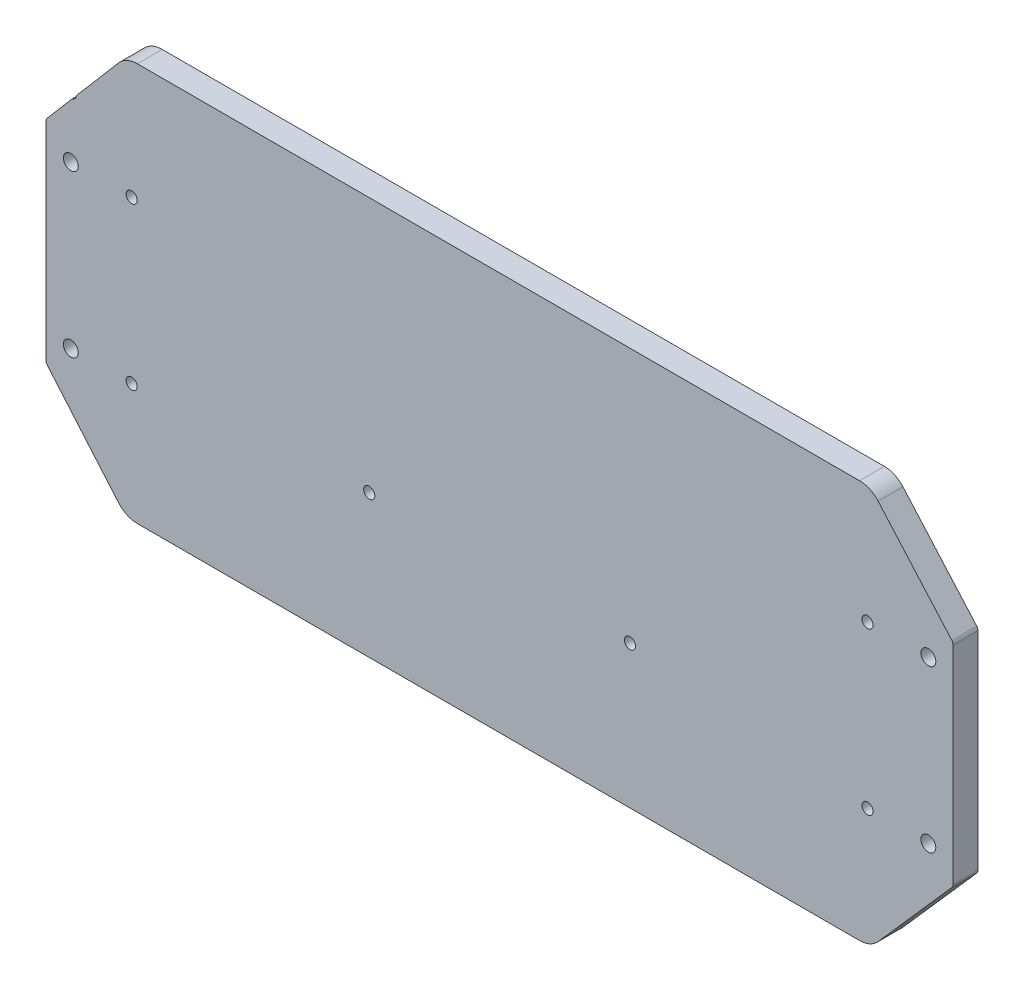
SolidWorks part; units mm, degrees
ref_plane "Plan de face" through (0, 0, 0) normal (0, 0, 1) x (1, 0, 0)
ref_plane "Plan de dessus" through (0, 0, 0) normal (0, 1, 0) x (1, 0, 0)
ref_plane "Plan de droite" through (0, 0, 0) normal (1, 0, 0) x (0, 0, -1)
sketch "Esquisse1" plane through (0, 0, 0) normal (0, 0, 1) x (1, 0, 0)
  line L0 (-182.2, 42.5) -> (-150, 80.2)
  line L1 (-182.2, 42.5) -> (183.2, 42.5)
  line L2 (-182.2, 42.5) -> (-182.2, -42.5)
  line L3 (-182.2, -42.5) -> (183.2, -42.5)
  line L4 (183.2, 42.5) -> (183.2, -42.5)
  line L5 (-150, 80.2) -> (150, 80.2)
  line L6 (-150, 80.2) -> (-150, 42.5)
  line L7 (-150, 42.5) -> (150, 42.5)
  line L8 (150, 80.2) -> (150, 42.5)
  line L9 (-150, -42.5) -> (150, -42.5)
  line L10 (-150, -42.5) -> (-150, -80.2)
  line L11 (-150, -80.2) -> (150, -80.2)
  line L12 (150, -42.5) -> (150, -80.2)
  line L13 (150, 80.2) -> (183.2, 42.5)
  line L14 (183.2, -42.5) -> (150, -80.2)
  line L15 (-150, -80.2) -> (-182.2, -42.5)
  dimension "D1" = 85
  dimension "D2" = 365.4
  dimension "D3" = 300
  dimension "D4" = 300
  dimension "D5" = 32.2
  dimension "D6" = 32.2
  dimension "D7" = 37.7
  dimension "D8" = 37.7
  dimension "D9" = 150
  dimension "D10" = 42.5
extrude "Boss.-Extru.1" add sketch "Esquisse1" along normal blind 10 contours L4 L1 L2 L3 | L8 L5 L6 L1 | L6 L0 L1 | L12 L3 L10 L11 | L15 L10 L3 | L13 L8 L1 | L14 L3 L12 region at (-160.7333, 55.0667, 0) region at (0.5, 0, 0) region at (0, 61.35, 0) region at (-160.7333, -55.0667, 0) region at (161.0667, 55.0667, 0) region at (0, -61.35, 0) region at (161.0667, -55.0667, 0)
sketch "Esquisse2" plane through (0, 0, 10) normal (0, 0, 1) x (1, 0, 0)
  line L1 (-182.2, 22.5) -> (-162.2, 22.5)
  line L2 (-182.2, 22.5) -> (-182.2, 42.5)
  line L3 (-182.2, 42.5) -> (-162.2, 42.5)
  line L4 (-162.2, 22.5) -> (-162.2, 42.5)
  line L5 (163.2, 22.5) -> (183.2, 22.5)
  line L6 (163.2, 22.5) -> (163.2, 42.5)
  line L7 (163.2, 42.5) -> (183.2, 42.5)
  line L8 (183.2, 22.5) -> (183.2, 42.5)
  line L9 (163.2, -22.5) -> (183.2, -22.5)
  line L10 (163.2, -22.5) -> (163.2, -42.5)
  line L11 (163.2, -42.5) -> (183.2, -42.5)
  line L12 (183.2, -22.5) -> (183.2, -42.5)
  line L13 (-182.2, -22.5) -> (-162.2, -22.5)
  line L14 (-182.2, -22.5) -> (-182.2, -42.5)
  line L15 (-182.2, -42.5) -> (-162.2, -42.5)
  line L16 (-162.2, -22.5) -> (-162.2, -42.5)
  line L17 (183.2, 42.5) -> (183.2, -42.5) construction
  line L18 (-182.2, 42.5) -> (-182.2, -42.5) construction
  dimension "D1" = 20
  dimension "D2" = 20
  dimension "D3" = 20
  dimension "D4" = 20
  dimension "D5" = 20
  dimension "D6" = 20
  dimension "D7" = 20
  dimension "D8" = 20
  dimension "D9" = 20
  dimension "D10" = 20
  dimension "D11" = 20
  dimension "D12" = 20
  dimension "D13" = 0
  dimension "D14" = 0
  dimension "D15" = 0
  dimension "D16" = 0
sketch "Esquisse3" plane through (0, 0, 10) normal (0, 0, 1) x (1, 0, 0)
  line L0 (-182.2, 42.5) -> (-162.2, 42.5) construction
  line L2 (-162.2, 22.5) -> (-162.2, 42.5) construction
  line L4 (-182.2, -22.5) -> (-162.2, -22.5) construction
  line L5 (-162.2, -22.5) -> (-162.2, -42.5) construction
  line L8 (163.2, -22.5) -> (183.2, -22.5) construction
  line L9 (163.2, -22.5) -> (163.2, -42.5) construction
  line L12 (163.2, 22.5) -> (163.2, 42.5) construction
  line L13 (163.2, 42.5) -> (183.2, 42.5) construction
  circle A0 centre (-147.7, 32.5) radius 2.25
  circle A1 centre (-172.2, 32.5) radius 3
  circle A2 centre (-172.2, 57) radius 2.25
  circle A3 centre (-172.2, -32.5) radius 3
  circle A4 centre (-147.7, -32.5) radius 2.25
  circle A6 centre (173.2, -32.5) radius 3
  circle A7 centre (148.7, -32.5) radius 2.25
  circle A9 centre (173.2, 32.5) radius 3
  circle A10 centre (148.7, 32.5) radius 2.25
  dimension "D1" = 6
  dimension "D5" = 4.5
  dimension "D6" = 4.5
  dimension "D10" = 6
  dimension "D13" = 4.5
  dimension "D14" = 14.5
  dimension "D17" = 14.5
  dimension "D19" = 6
  dimension "D27" = 4.5
  dimension "D28" = 4.5
  dimension "D30" = 6
  dimension "D15" = 14.5
  dimension "D7" = 14.5
  dimension "D2" = 10
  dimension "D3" = 10
  dimension "D4" = 10
  dimension "D8" = 14.5
  dimension "D9" = 10
  dimension "D11" = 10
  dimension "D12" = 10
  dimension "D16" = 10
  dimension "D20" = 10
  dimension "D21" = 10
  dimension "D26" = 10
  dimension "D31" = 10
  dimension "D32" = 10
  dimension "D33" = 10
extrude "Enlèv. mat.-Extru.1" cut sketch "Esquisse3" against normal blind 10
sketch "Esquisse4" plane through (0, 0, 10) normal (0, 0, 1) x (1, 0, 0)
  line L0 (-182.2, 42.5) -> (-182.2, -42.5) construction
  line L1 (-150, -80.2) -> (150, -80.2) construction
  line L2 (183.2, 42.5) -> (183.2, -42.5) construction
  circle A0 centre (-52, -22.7) radius 2.25
  circle A1 centre (53, -22.7) radius 2.25
  dimension "D1" = 4.5
  dimension "D2" = 4.5
  dimension "D3" = 130.2
  dimension "D4" = 57.5
  dimension "D5" = 57.5
  dimension "D6" = 130.2
extrude "Enlèv. mat.-Extru.2" cut sketch "Esquisse4" against normal blind 10
fillet "Congé1" radius 10 4 edges at (-150, 80.2, 5) (150, 80.2, 5) (150, -80.2, 5) (-150, -80.2, 5)
fillet "Congé2" radius 2 4 edges at (-182.2, -42.5, 5) (-182.2, 42.5, 5) (183.2, -42.5, 5) (183.2, 42.5, 5)
